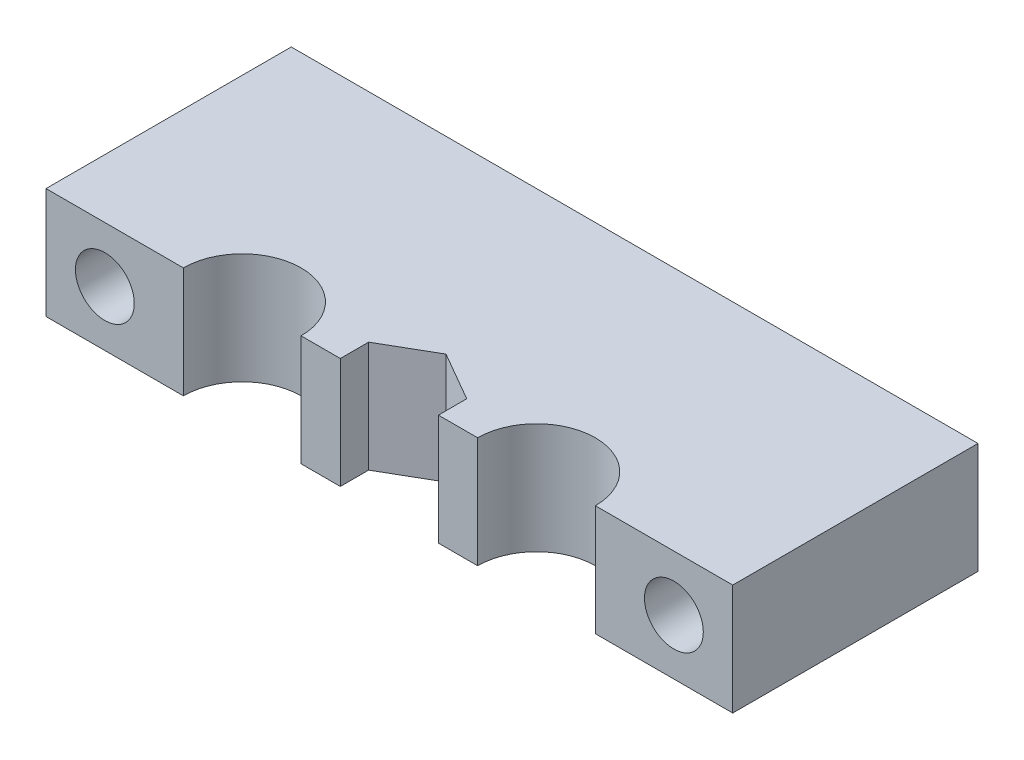
SolidWorks part; units mm, degrees
ref_plane "Front Plane" through (0, 0, 0) normal (0, 0, 1) x (1, 0, 0)
ref_plane "Top Plane" through (0, 0, 0) normal (0, 1, 0) x (1, 0, 0)
ref_plane "Right Plane" through (0, 0, 0) normal (1, 0, 0) x (0, 0, -1)
sketch "Sketch1" plane through (0, 0, 0) normal (0, 1, 0) x (1, 0, 0)
  line L0 (35, 0) -> (35, 25) construction
  line L5 (0, 0) -> (70, 0) construction
  line L6 (0, 0) -> (0, 25) construction
  line L13 (0, 25) -> (70, 25) construction
  line L14 (70, 0) -> (70, 25) construction
  line L15 (56, 0) -> (70, 0)
  line L16 (30, 2.8868) -> (30, -2.8868) construction
  line L17 (30, -2.8868) -> (35, -5.7735) construction
  line L18 (35, -5.7735) -> (40, -2.8868) construction
  line L19 (40, -2.8868) -> (40, 2.8868) construction
  line L20 (40, 2.8868) -> (35, 5.7735) construction
  line L21 (35, 5.7735) -> (30, 2.8868) construction
  line L22 (70, 0) -> (70, 25)
  line L23 (70, 25) -> (0, 25)
  line L24 (0, 25) -> (0, 0)
  line L25 (0, 0) -> (14, 0)
  line L26 (26, 0) -> (30, 0)
  line L27 (30, 0) -> (30, 2.8868)
  line L28 (30, 2.8868) -> (35, 5.7735)
  line L29 (35, 5.7735) -> (40, 2.8868)
  line L30 (40, 2.8868) -> (40, 0)
  line L31 (40, 0) -> (44, 0)
  circle A2 centre (20, 0) radius 6 construction
  circle A3 centre (35, 0) radius 5 construction
  circle A4 centre (50, 0) radius 6 construction
  arc A5 (14, 0) -> (26, 0) centre (20, 0) cw
  arc A6 (44, 0) -> (56, 0) centre (50, 0) cw
  point P7 (35, 0)
  dimension "D3" = 12
  dimension "D4" = 25
  dimension "D1" = 15
  dimension "D2" = 70
  dimension "D5" = 10
extrude "Boss-Extrude1" add sketch "Sketch1" along normal blind 11.3
sketch "Sketch2" plane through (0, 0, -25) normal (0, 0, -1) x (-1, 0, 0)
  line L0 (-35, 11.3) -> (-35, 0) construction
  line L1 (-70, 11.3) -> (0, 11.3) construction
  line L2 (-70, 0) -> (0, 0) construction
  line L3 (0, 5.65) -> (-6, 5.65) construction
  line L4 (0, 11.3) -> (0, 0) construction
  circle A0 centre (-6, 5.65) radius 3
  circle A1 centre (-64, 5.65) radius 3
  dimension "D1" = 6
  dimension "D2" = 6
extrude "Cut-Extrude1" cut sketch "Sketch2" against normal through all
